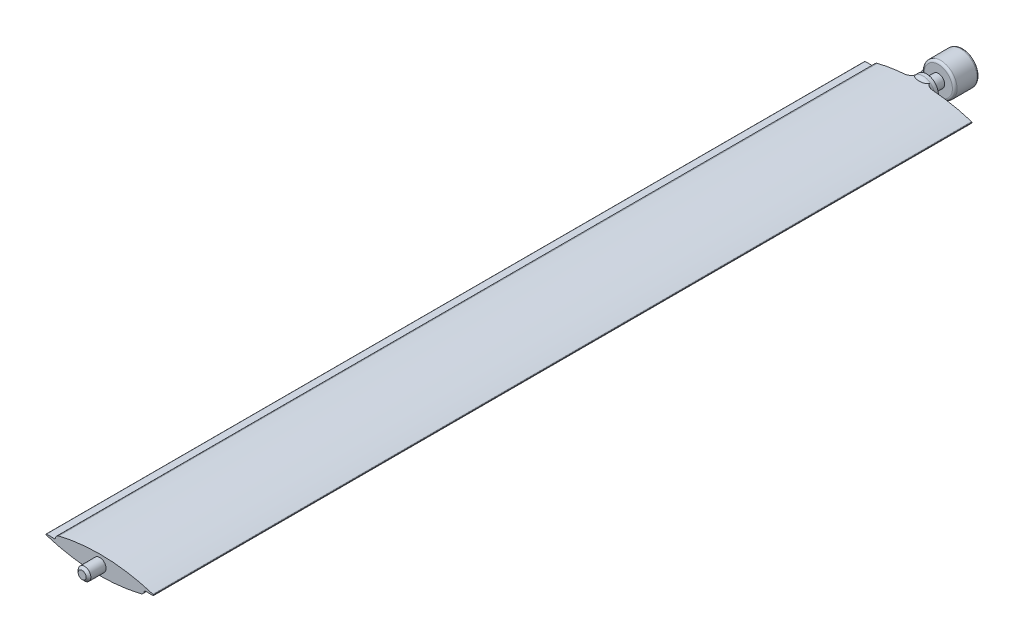
SolidWorks part; units mm, degrees
material "PVC 0.007 Plasticized"
ref_plane "Front Plane" through (0, 0, 0) normal (0, 0, 1) x (1, 0, 0)
ref_plane "Top Plane" through (0, 0, 0) normal (0, 1, 0) x (1, 0, 0)
ref_plane "Right Plane" through (0, 0, 0) normal (1, 0, 0) x (0, 0, -1)
sketch "Sketch1" plane through (0, 0, 0) normal (0, 0, 1) x (1, 0, 0)
  circle A0 centre (0, 14.4815) radius 1.35
  dimension "D1" = 2.7
extrude "Boss-Extrude1" add sketch "Sketch1" against normal blind 182.5
sketch "Sketch2" plane through (0, 0, -182.5) normal (0, 0, -1) x (-1, 0, 0)
  circle A0 centre (0, 14.4815) radius 3.5
  dimension "D1" = 7
extrude "Boss-Extrude2" add sketch "Sketch2" along normal blind 5.25
sketch "Sketch3" plane through (0, 0, -182.5) normal (0, 0, 1) x (1, 0, 0)
  circle A0 centre (0, 14.4815) radius 2.5
  dimension "D1" = 5
extrude "Boss-Extrude3" add sketch "Sketch3" along normal blind 1.75 from offset 2.5
chamfer "Chamfer1" distance 0.5 angle 45 1 edges at (1.35, 14.4815, 0)
fillet "Fillet1" radius 0.5 2 edges at (-3.5, 14.4815, -182.5) (-3.5, 14.4815, -187.75)
sketch "Sketch4" plane through (0, 0, -178.25) normal (0, 0, 1) x (1, 0, 0)
  line L0 (-11.5, 14.4815) -> (11.5, 14.4815) construction
  line L1 (0, 49.7672) -> (0, -20.8042) construction
  line L2 (0, 16.4815) -> (0, 12.4815) construction
  arc A0 (11.3259, 14.2433) -> (11.3259, 14.7197) centre (11.25, 14.4815) ccw
  arc A1 (-11.3259, 14.7197) -> (-11.3259, 14.2433) centre (-11.25, 14.4815) ccw
  arc A2 (11.3259, 14.7197) -> (-11.3259, 14.7197) centre (0, -20.8042) ccw
  arc A4 (-11.3259, 14.2433) -> (11.3259, 14.2433) centre (0, 49.7672) ccw
  dimension "D3" = 0.5
  dimension "D1" = 23
  dimension "D2" = 4
extrude "Boss-Extrude4" add sketch "Sketch4" along normal blind 174.5
fillet "Fillet2" radius 1 2 edges at (0, 11.9815, -178.25) (0, 16.9815, -178.25)
fillet "Fillet3" radius 1 2 edges at (-2.5, 14.4815, -178.25) (2.5, 14.4815, -178.25)
ref_plane "Plane1" through (0, 0, -187.25) normal (0, 0, 1) x (1, 0, 0)
sketch "Sketch5" plane through (0, 0, -187.25) normal (0, 0, 1) x (1, 0, 0)
  line L0 (0, 14.4815) -> (0, 17.9815) construction
  line L1 (0, 14.4815) -> (-5.6569, 8.8246) construction
  line L2 (-7.5402, 10.2302) -> (-2.8049, 16.5749)
  line L3 (-4.2513, 6.9413) -> (2.0934, 11.6766)
  arc A0 (2.0934, 11.6766) -> (-2.8049, 16.5749) centre (0, 14.4815) ccw
  circle A1 centre (0, 14.4815) radius 3.5 construction
  arc A2 (-7.5402, 10.2302) -> (-4.2513, 6.9413) centre (-5.6569, 8.8246) ccw
  dimension "D3" = 4.7
  dimension "D1" = 225
  dimension "D2" = 8
extrude "Boss-Extrude5" add sketch "Sketch5" along normal blind 1.5
sketch "Sketch6" plane through (0, 0, -185.75) normal (0, 0, 1) x (1, 0, 0)
  circle A0 centre (-5.6569, 8.8246) radius 1.5
  dimension "D1" = 3
extrude "Boss-Extrude6" add sketch "Sketch6" along normal blind 2
sketch "Sketch7" plane through (0, 0, -183.75) normal (0, 0, 1) x (1, 0, 0)
  circle A0 centre (-5.6569, 8.8246) radius 2
  dimension "D1" = 4
extrude "Boss-Extrude7" add sketch "Sketch7" along normal blind 1
chamfer "Chamfer2" distance 0.75 angle 45 1 edges at (-3.6569, 8.8246, -182.75)
sketch "Sketch8" plane through (0, 0, -182.75) normal (0, 0, 1) x (1, 0, 0)
  line L1 (-3.4069, 8.3246) -> (-7.9069, 8.3246)
  line L2 (-3.4069, 8.3246) -> (-3.4069, 9.3246)
  line L3 (-3.4069, 9.3246) -> (-7.9069, 9.3246)
  line L4 (-7.9069, 8.3246) -> (-7.9069, 9.3246)
  line L5 (-3.4069, 8.3246) -> (-7.9069, 9.3246) construction
  line L6 (-3.4069, 9.3246) -> (-7.9069, 8.3246) construction
  circle A0 centre (-5.6569, 8.8246) radius 2.25 construction
  point P0 (-5.6569, 8.8246)
  dimension "D1" = 1
extrude "Cut-Extrude1" cut sketch "Sketch8" against normal blind 2
sketch "Sketch9" plane through (0, 0, -187.75) normal (0, 0, -1) x (-1, 0, 0)
  line L0 (-2.55, 14.4815) -> (2.55, 14.4815) construction
  line L1 (-2.0248, 16.0315) -> (2.0248, 16.0315)
  line L2 (-2.0248, 12.9315) -> (2.0248, 12.9315)
  arc A0 (-2.0248, 16.0315) -> (-2.0248, 12.9315) centre (0, 14.4815) ccw
  arc A1 (2.0248, 12.9315) -> (2.0248, 16.0315) centre (0, 14.4815) ccw
  dimension "D1" = 5.1
  dimension "D2" = 3.1
extrude "Cut-Extrude2" cut sketch "Sketch9" against normal blind 4.5
chamfer "Chamfer3" distance 0.2 angle 45 4 edges at (0, 12.9315, -187.75) (-2.55, 14.4815, -187.75) (0, 16.0315, -187.75) (2.55, 14.4815, -187.75)
fillet "Fillet4" radius 0.5 3 edges at (-1.0789, 9.309, -187.25) (-7.3186, 7.1629, -187.25) (-5.1725, 13.4026, -187.25)
sketch "Sketch10" plane through (0, 0, -3.75) normal (0, 0, 1) x (1, 0, 0)
  line L1 (-11.5, 14.4815) -> (-9.5, 14.4815)
  line L2 (-11.5, 14.4815) -> (-11.5, 15.2509)
  line L3 (-11.5, 15.2509) -> (-9.5, 15.2509)
  line L4 (-9.5, 14.4815) -> (-9.5, 15.2509)
  line L5 (11.5, 14.4815) -> (9.5, 14.4815)
  line L6 (11.5, 14.4815) -> (11.5, 13.7121)
  line L7 (11.5, 13.7121) -> (9.5, 13.7121)
  line L8 (9.5, 14.4815) -> (9.5, 13.7121)
  arc A0 (-11.3259, 14.7197) -> (-11.3259, 14.2433) centre (-11.25, 14.4815) ccw construction
  arc A1 (11.3259, 14.7197) -> (-11.3259, 14.7197) centre (0, -20.8042) ccw construction
  arc A2 (11.3259, 14.2433) -> (11.3259, 14.7197) centre (11.25, 14.4815) ccw construction
  arc A4 (-11.3259, 14.2433) -> (11.3259, 14.2433) centre (0, 49.7672) ccw construction
  dimension "D1" = 2
  dimension "D2" = 2
extrude "Cut-Extrude3" cut sketch "Sketch10" against normal up to next
fillet "Fillet5" radius 1 2 edges at (9.5, 13.7121, -91) (-9.5, 15.2509, -91)
fillet "Fillet6" radius 0.1 2 edges at (11.5, 14.4815, -91) (-11.5, 14.4815, -91)
fillet "Fillet7" radius 0.15 2 edges at (9.5, 14.4815, -91) (-9.5, 14.4815, -91)
